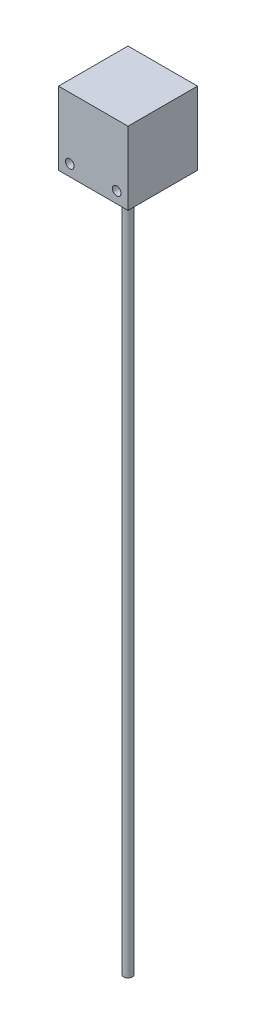
SolidWorks part; units mm, degrees
ref_plane "前视基准面" through (0, 0, 0) normal (0, 0, 1) x (1, 0, 0)
ref_plane "上视基准面" through (0, 0, 0) normal (0, 1, 0) x (1, 0, 0)
ref_plane "右视基准面" through (0, 0, 0) normal (1, 0, 0) x (0, 0, -1)
other "Configuration Table"
sketch "草图1" plane through (0, 0, 0) normal (0, 0, 1) x (1, 0, 0)
  line L0 (0, 0) -> (40, 0)
  line L1 (40, 0) -> (40, -42)
  line L2 (0, 0) -> (0, -42)
  line L3 (0, -42) -> (17.5, -42)
  line L4 (17.5, -42) -> (22.5, -42)
  line L5 (22.5, -42) -> (22.5, -443)
  line L6 (22.5, -443) -> (17.5, -443)
  line L7 (17.5, -443) -> (17.5, -42)
  line L8 (22.5, -42) -> (40, -42)
  line L9 (20, -42) -> (20, -443)
  dimension "D1" = 40
  dimension "D2" = 42
extrude "凸台-拉伸1" add sketch "草图1" along normal mid plane 40 contours L4 L8 L1 L0 L2 L3 region at (20, -21, 0)
revolve "旋转1" add sketch "草图1<3>" angle 360 about L9 region at (21.25, -242.5, 0)
sketch "草图1<3>" plane through (0, 0, 0) normal (0, 0, 1) x (1, 0, 0) same geometry as "草图1"
sketch "草图2" plane through (0, 0, 20) normal (0, 0, 1) x (1, 0, 0)
  line L0 (20, -42) -> (20, -35.5)
  line L1 (0, -42) -> (40, -42) construction
  line L2 (20, -35.5) -> (6.5, -35.5)
  circle A0 centre (6.5, -35.5) radius 2.5
  circle A1 centre (33.5, -35.5) radius 2.5
  dimension "D1" = 27
  dimension "D2" = 6.5
extrude "切除-拉伸1" cut sketch "草图2" against normal through all contours A0 | A1 region at (4.0707, -35.5, 20) region at (33.5, -35.5, 20)
